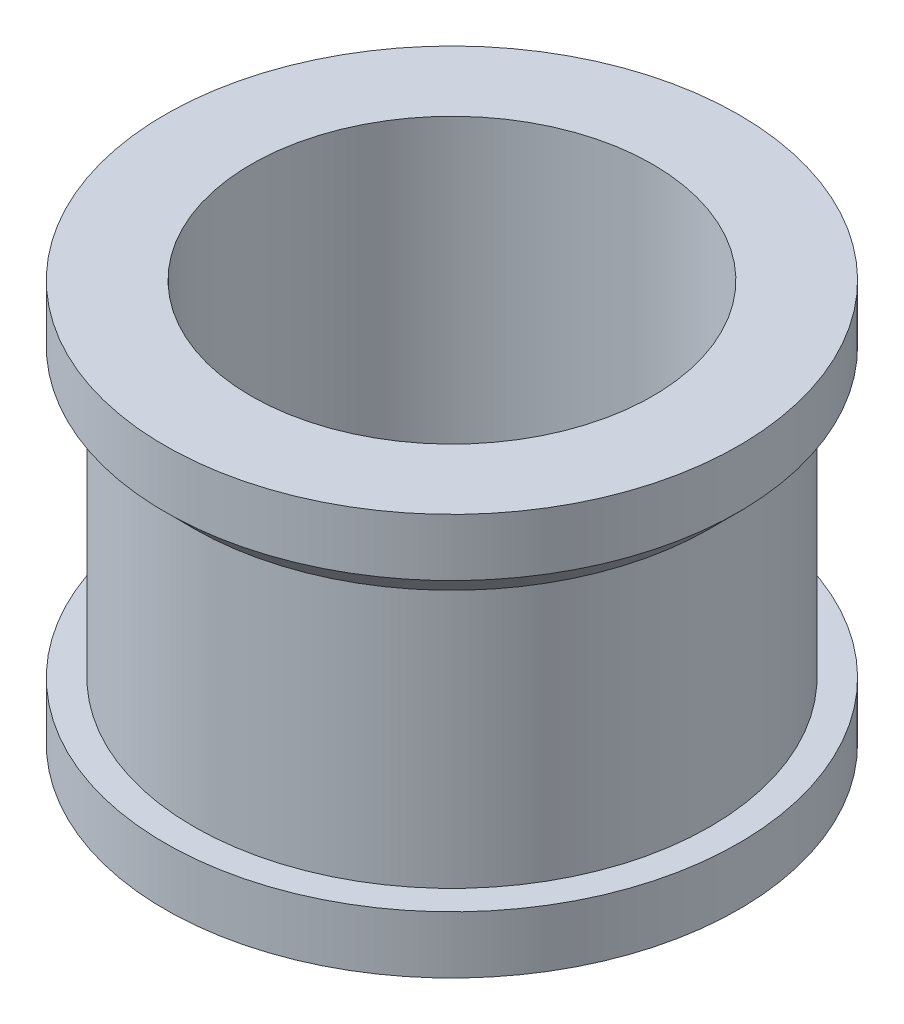
SolidWorks part; units mm, degrees
ref_plane "Front Plane" through (0, 0, 0) normal (0, 0, 1) x (1, 0, 0)
ref_plane "Top Plane" through (0, 0, 0) normal (0, 1, 0) x (1, 0, 0)
ref_plane "Right Plane" through (0, 0, 0) normal (1, 0, 0) x (0, 0, -1)
sketch "Sketch1" plane through (0, 0, 0) normal (0, 0, 1) x (1, 0, 0)
  line L0 (0, 0.1) -> (0, 13.9558) construction
  line L1 (7, 0) -> (7, 14)
  line L2 (7, 14) -> (10, 14)
  line L3 (10, 14) -> (10, 12)
  line L4 (10, 12) -> (9, 12)
  line L5 (9, 12) -> (9, 2)
  line L6 (9, 2) -> (10, 2)
  line L7 (10, 2) -> (10, 0)
  line L8 (10, 0) -> (7, 0)
  line L9 (7, 7) -> (9, 7) construction
  dimension "D1" = 9
  dimension "D2" = 2
  dimension "D3" = 1
  dimension "D4" = 10
revolve "Revolve1" add sketch "Sketch1" angle 360 about L0
chamfer "Chamfer1" distance 1 angle 45 1 edges at (0, 12, -9)
